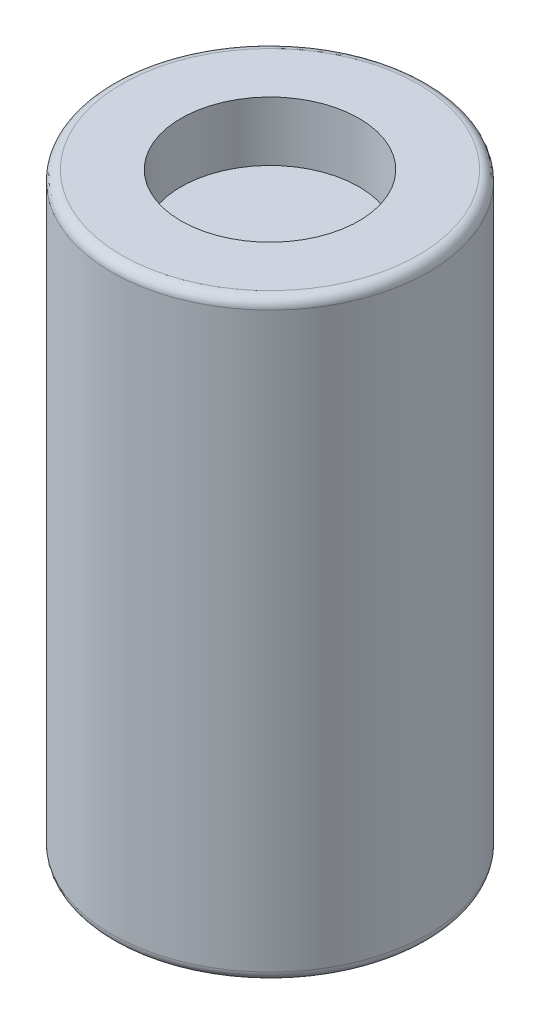
SolidWorks part; units mm, degrees
ref_plane "Front Plane" through (0, 0, 0) normal (0, 0, 1) x (1, 0, 0)
ref_plane "Top Plane" through (0, 0, 0) normal (0, 1, 0) x (1, 0, 0)
ref_plane "Right Plane" through (0, 0, 0) normal (1, 0, 0) x (0, 0, -1)
sketch "Sketch1" plane through (0, 0, 0) normal (0, 1, 0) x (1, 0, 0)
  circle A4 centre (0, 0) radius 25.4
  dimension "D1" = 50.8
extrude "Boss-Extrude1" add sketch "Sketch1" along normal blind 95.25 contours A4
fillet "Fillet1" radius 1.5875 2 edges at (0, 0, 25.4) (0, 95.25, 25.4)
sketch "Sketch2" plane through (0, 95.25, 0) normal (0, 1, 0) x (1, 0, 0)
  circle A0 centre (0, 0) radius 14.2875
  dimension "D1" = 28.575
extrude "Cut-Extrude1" cut sketch "Sketch2" against normal blind 9.525
sketch "Sketch3" plane through (0, 0, 0) normal (0, -1, 0) x (1, 0, 0)
  circle A0 centre (0, 0) radius 14.2875
  dimension "D1" = 28.575
extrude "Cut-Extrude2" cut sketch "Sketch3" against normal blind 9.525
